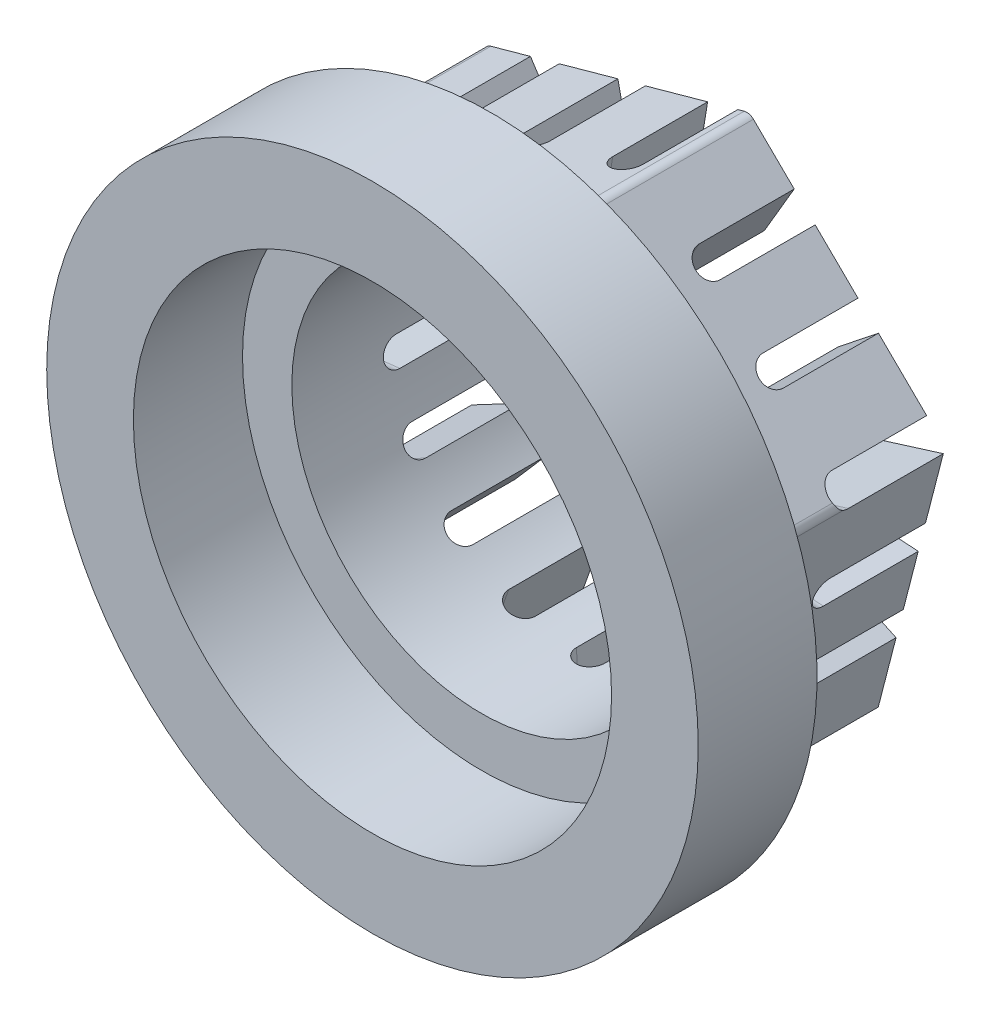
SolidWorks part; units mm, degrees
material "AISI Type 316L stainless steel"
ref_plane "Front Plane" through (0, 0, 0) normal (0, 0, 1) x (1, 0, 0)
ref_plane "Top Plane" through (0, 0, 0) normal (0, 1, 0) x (1, 0, 0)
ref_plane "Right Plane" through (0, 0, 0) normal (1, 0, 0) x (0, 0, -1)
sketch "Sketch1" plane through (0, 0, 0) normal (0, 0, 1) x (1, 0, 0)
  circle A0 centre (0, 0) radius 21.7995
  dimension "D1" = 43.5991
extrude "Boss-Extrude1" add sketch "Sketch1" along normal blind 20.6502
sketch "Sketch2" plane through (0, 0, 20.6502) normal (0, 0, 1) x (1, 0, 0)
  circle A0 centre (0, 0) radius 12.7
  dimension "D1" = 25.4
extrude "Cut-Extrude1" cut sketch "Sketch2" against normal blind 20.6502
sketch "Sketch3" plane through (0, 0, 20.6502) normal (0, 0, 1) x (1, 0, 0)
  circle A0 centre (0, 0) radius 16
  dimension "D1" = 32
extrude "Cut-Extrude2" cut sketch "Sketch3" against normal blind 7.3025
sketch "Sketch4" plane through (0, 0, 0) normal (0, 0, -1) x (-1, 0, 0)
  line L1 (17.6618, -4.9073) -> (13.0808, 12.8419)
  line L2 (13.0808, 12.8419) -> (-4.581, 17.7492)
  line L3 (-4.581, 17.7492) -> (-17.6618, 4.9073)
  line L4 (-17.6618, 4.9073) -> (-13.0808, -12.8419)
  line L5 (-13.0808, -12.8419) -> (4.581, -17.7492)
  line L6 (4.581, -17.7492) -> (17.6618, -4.9073)
  circle A1 centre (0, 0) radius 15.875 construction
  dimension "D1" = 31.75
extrude "Cut-Extrude3" cut sketch "Sketch4" against normal blind 12.7 flip side to cut
sketch "Sketch5" plane through (-15.3713, 3.9673, 0) normal (-0.9683, 0.2499, 0) x (0, 0, 1)
  line L0 (0, 0) -> (12.7, 0) construction
  line L1 (12.7, -9.1654) -> (12.7, 9.1654) construction
  line L2 (6.35, 0.9525) -> (0, 0.9525)
  line L3 (0, -9.1654) -> (0, 9.1654) construction
  line L4 (0, 0.9525) -> (0, -0.9525)
  line L5 (0, -0.9525) -> (6.35, -0.9525)
  arc A1 (6.35, 0.9525) -> (6.35, -0.9525) centre (6.35, 0) cw
  point P6 (0, 0)
extrude "Cut-Extrude4" cut sketch "Sketch5" against normal blind 9.8552 and the other way blind 9.8552
pattern_circular "CirPattern1" count 17 over 360 about axis through (0, 0, 13.3477) along (0, 0, 1) of "Cut-Extrude4" reverse direction yes
fillet "Fillet1" radius 0.635 6 edges at (-17.6618, -4.9073, 6.35) (-13.0808, 12.8419, 6.35) (4.581, 17.7492, 6.35) (17.6618, 4.9073, 9.9086) (13.0808, -12.8419, 9.9086) (-4.581, -17.7492, 6.35)
ref_axis "Axis1" through (0, 0, 13.3477) along (0, 0, 1)
